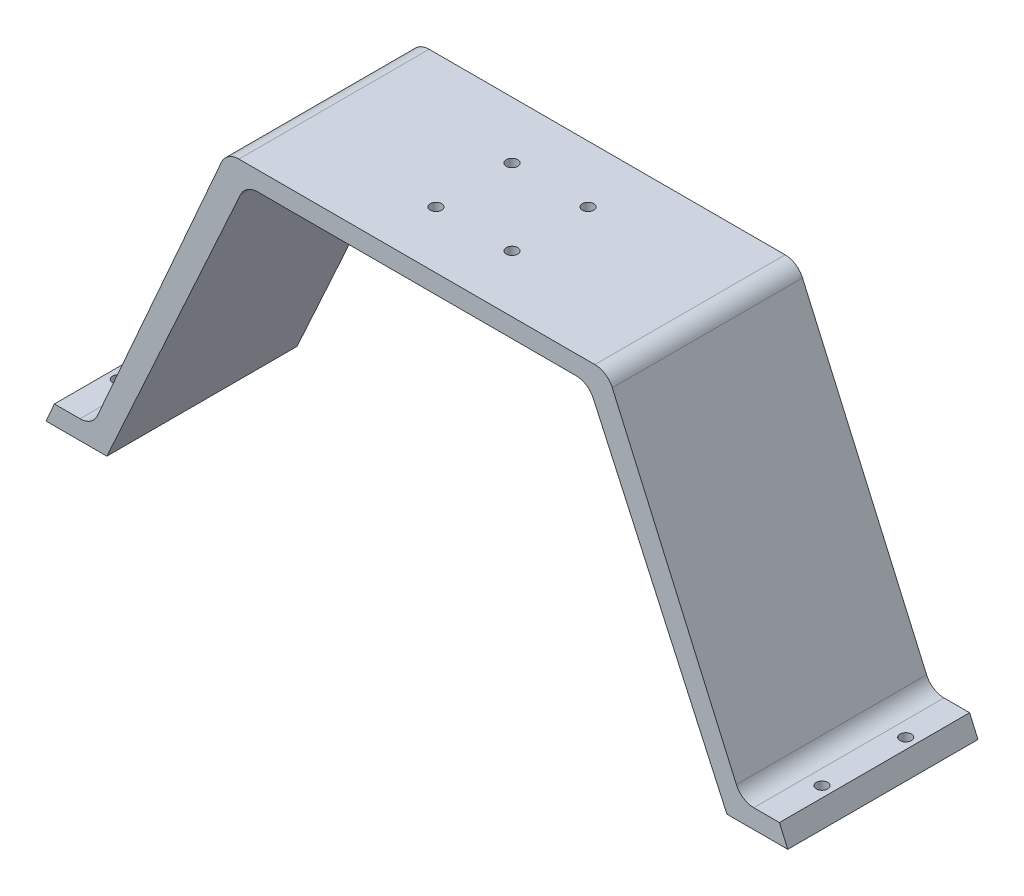
SolidWorks part; units mm, degrees
ref_plane "Front Plane" through (0, 0, 0) normal (0, 0, 1) x (1, 0, 0)
ref_plane "Top Plane" through (0, 0, 0) normal (0, 1, 0) x (1, 0, 0)
ref_plane "Right Plane" through (0, 0, 0) normal (1, 0, 0) x (0, 0, -1)
sketch "Sketch1" plane through (0, 0, 0) normal (0, 0, 1) x (1, 0, 0)
  line L0 (-87.5, 0) -> (87.5, 0)
  line L1 (-87.5, 0) -> (-50.05, 85)
  line L2 (-50.05, 85) -> (50.05, 85)
  line L3 (50.05, 85) -> (87.5, 0)
  point P4 (0, 0)
  dimension "D1" = 175
  dimension "D2" = 100.1
  dimension "D3" = 50.05
  dimension "D4" = 85
extrude "Boss-Extrude2" add sketch "Sketch1" along normal blind 50 contours L1 L2 L3 L0
sketch "Sketch3" plane through (0, 0, 50) normal (0, 0, 1) x (1, 0, 0)
  line L0 (-81.5, 0) -> (81.5, 0)
  line L1 (-87.5, 0) -> (87.5, 0) construction
  line L2 (81.5, 0) -> (45.05, 80)
  line L3 (45.05, 80) -> (-45.05, 80)
  line L4 (-45.05, 80) -> (-81.5, 0)
  line L5 (-50.05, 85) -> (50.05, 85) construction
  dimension "D1" = 163
  dimension "D2" = 6
  dimension "D3" = 90.1
  dimension "D4" = 45.05
  dimension "D5" = 5
extrude "Cut-Extrude1" cut sketch "Sketch3" against normal blind 50
fillet "Fillet1" radius 5 2 edges at (45.05, 80, 25) (-45.05, 80, 25)
sketch "Sketch5" plane through (73.2758, 32.2845, 0) normal (0.9151, 0.4032, 0) x (0, 0, -1)
  line L0 (0, 57.6053) -> (0, -35.2791) construction
  line L1 (-50, -35.2791) -> (0, -35.2791)
  line L2 (-50, -35.2791) -> (-50, -29.8151)
  line L3 (-50, -29.8151) -> (0, -29.8151)
  line L4 (0, -35.2791) -> (0, -29.8151)
  dimension "D1" = 5.464
sketch "Sketch8" plane through (0, 0, 0) normal (0, 1, 0) x (1, 0, 0)
  line L0 (93.2771, -25.8796) -> (149.3121, -25.8796)
  point P2 (0, 0)
sketch "Sketch9" plane through (0, 0, 0) normal (0, 1, 0) x (1, 0, 0)
  line L0 (-93.9767, -25.7952) -> (-133.9417, -25.7952)
sketch "Sketch10" plane through (-73.2758, 32.2845, 0) normal (-0.9151, 0.4032, 0) x (0, 0, 1)
  line L0 (0, -35.2791) -> (0, 57.6053) construction
  line L1 (50, -35.2791) -> (0, -35.2791)
  line L2 (50, -35.2791) -> (50, -29.8191)
  line L3 (50, -29.8191) -> (0, -29.8191)
  line L4 (0, -35.2791) -> (0, -29.8191)
  dimension "D1" = 5.46
extrude "Boss-Extrude4" add sketch "Sketch10" along direction (-1, 0, 0) on the side of the normal blind 10
extrude "Boss-Extrude5" add sketch "Sketch5" along direction (1, 0, 0) on the side of the normal blind 10 contours L3 L4 L1 L2
sketch "Sketch11" plane through (0, 4.9965, 0) normal (0, 1, 0) x (1, 0, 0)
  line L0 (-97.5, 0) -> (-97.5, -50) construction
  line L1 (-95.2986, -50) -> (-85.2986, -50) construction
  circle A0 centre (-92.5, -14) radius 1.5
  circle A1 centre (-92.5, -36) radius 1.5
  dimension "D1" = 22
  dimension "D2" = 5
  dimension "D3" = 14
extrude "Cut-Extrude2" cut sketch "Sketch11" against normal blind 10
sketch "Sketch12" plane through (0, 5.0002, 0) normal (0, 1, 0) x (1, 0, 0)
  line L0 (97.5, -50) -> (97.5, 0) construction
  line L1 (95.297, -50) -> (85.297, -50) construction
  circle A0 centre (92.5, -14) radius 1.5
  circle A1 centre (92.5, -36) radius 1.5
  dimension "D1" = 22
  dimension "D2" = 5
  dimension "D3" = 14
extrude "Cut-Extrude3" cut sketch "Sketch12" against normal blind 10
fillet "Fillet2" radius 5 2 edges at (85.297, 5.0002, 25) (-85.2986, 4.9965, 25)
fillet "Fillet3" radius 5 2 edges at (50.05, 85, 25) (-50.05, 85, 25)
sketch "Sketch13" plane through (0, 85, 0) normal (0, 1, 0) x (1, 0, 0)
  line L1 (-46.7892, 0) -> (-46.7892, -50) construction
  line L3 (-46.7892, 0) -> (46.7892, 0) construction
  line L4 (-46.7892, -50) -> (46.7892, -50) construction
  circle A0 centre (-9.9992, -15) radius 1.5
  circle A1 centre (10.0008, -15) radius 1.5
  circle A2 centre (-9.9992, -35) radius 1.5
  circle A3 centre (10.0008, -35) radius 1.5
  dimension "D1" = 20
  dimension "D2" = 20
  dimension "D3" = 20
  dimension "D4" = 20
  dimension "D5" = 36.79
  dimension "D6" = 15
extrude "Cut-Extrude5" cut sketch "Sketch13" against normal blind 10
sketch "Sketch14" plane through (0, 80, 0) normal (0, -1, 0) x (1, 0, 0)
  circle A0 centre (-9.9992, 35) radius 3
  circle A1 centre (-9.9992, 15) radius 3
  circle A2 centre (10.0008, 35) radius 3
  circle A3 centre (10.0008, 15) radius 3
extrude "Cut-Extrude6" cut sketch "Sketch14" against normal blind 2.5
